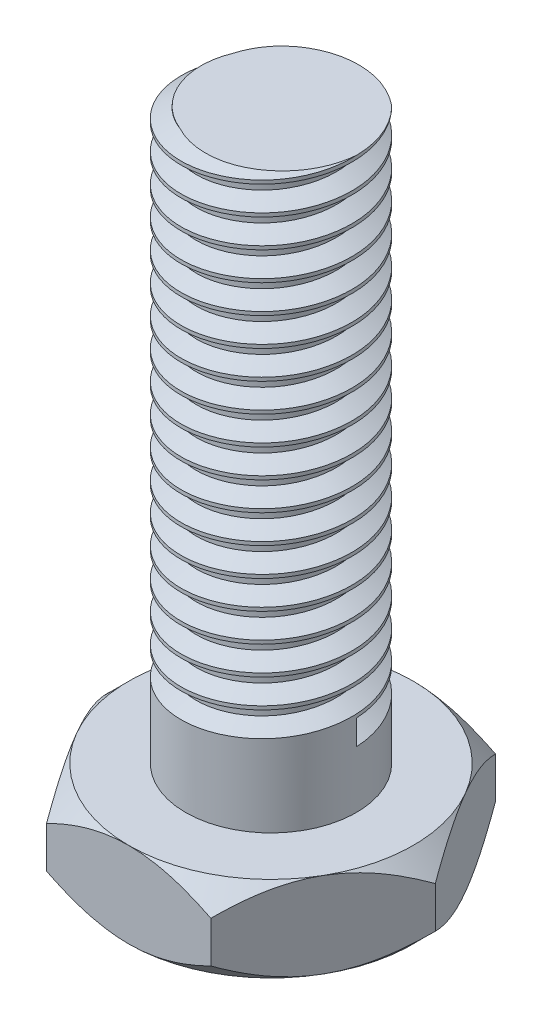
SolidWorks part; units mm, degrees
ref_plane "Front Plane" through (0, 0, 0) normal (0, 0, 1) x (1, 0, 0)
ref_plane "Top Plane" through (0, 0, 0) normal (0, 1, 0) x (1, 0, 0)
ref_plane "Right Plane" through (0, 0, 0) normal (1, 0, 0) x (0, 0, -1)
sketch "Sketch1" plane through (0, 0, 0) normal (0, 1, 0) x (1, 0, 0)
  line L1 (2.8868, 0) -> (1.4434, 2.5)
  line L2 (1.4434, 2.5) -> (-1.4434, 2.5)
  line L3 (-1.4434, 2.5) -> (-2.8868, 0)
  line L4 (-2.8868, 0) -> (-1.4434, -2.5)
  line L5 (-1.4434, -2.5) -> (1.4434, -2.5)
  line L6 (1.4434, -2.5) -> (2.8868, 0)
  circle A1 centre (0, 0) radius 2.5 construction
  dimension "D1" = 5
extrude "Boss-Extrude1" add sketch "Sketch1" along normal mid plane 1.5
sketch "Sketch2" plane through (0, 0.75, 0) normal (0, 1, 0) x (1, 0, 0)
  line L0 (1.4434, 2.5) -> (-1.4434, 2.5) construction
  circle A0 centre (0, 0) radius 2.5
extrude "Cut-Extrude2" cut sketch "Sketch2" against normal through all draft 45 flip side to cut
mirror "Mirror1" about plane through (0, 0, 0) normal (0, 1, 0) of "Cut-Extrude2" second plane through (0, 0, 0) second plane normal (0, 0, 1)
sketch "Sketch3" plane through (0, 0.75, 0) normal (0, 1, 0) x (1, 0, 0)
  circle A0 centre (0, 0) radius 1.5
  dimension "D1" = 3
extrude "Boss-Extrude2" add sketch "Sketch3" along normal blind 10
thread "Thread1" pitch 0.5 method cut profile "Thread Profile1" start angle 0, offset 1, length 0, pitch 0.5, diameter 3
ref_plane "Plane1" through (1.5, 1.75, 0) normal (0, 0, 1) x (1, 0, 0)
sketch "Thread Profile1" plane through (1.5, 1.75, 0) normal (0, 0, 1) x (1, 0, 0)
  line L0 (0, 0) -> (0, 0.5) construction
  line L11 (0, 0) -> (0, 0.4375)
  line L12 (0, 0.4375) -> (-0.2706, 0.2812)
  line L13 (-0.2706, 0.2812) -> (-0.2706, 0.1562)
  line L15 (-0.2706, 0.1562) -> (0, 0)
  line L17 (-0.2706, 0.2187) -> (0, 0.2187) construction
  point P2 (0, 0)
  dimension "Pitch" = 0.5
  dimension "Profile_Angle" = 60
  dimension "Profile_Land" = 0.125
  dimension "Profile_Height" = 0.2706
equation "\"Bolt shaft dia\" = 3.mm"
equation "\"bolt head dia\"= 5mm"
equation "\"bolt head thickness\"= 1.5mm"
equation "\"Bolt shaft length\"= 10mm"
equation "\"D1@Sketch1\"=\"bolt head dia\""
equation "\"D1@Boss-Extrude1\"=\"bolt head thickness\""
equation "\"D1@Sketch3\"=\"Bolt shaft dia\""
equation "\"D1@Boss-Extrude2\"=\"Bolt shaft length\""
